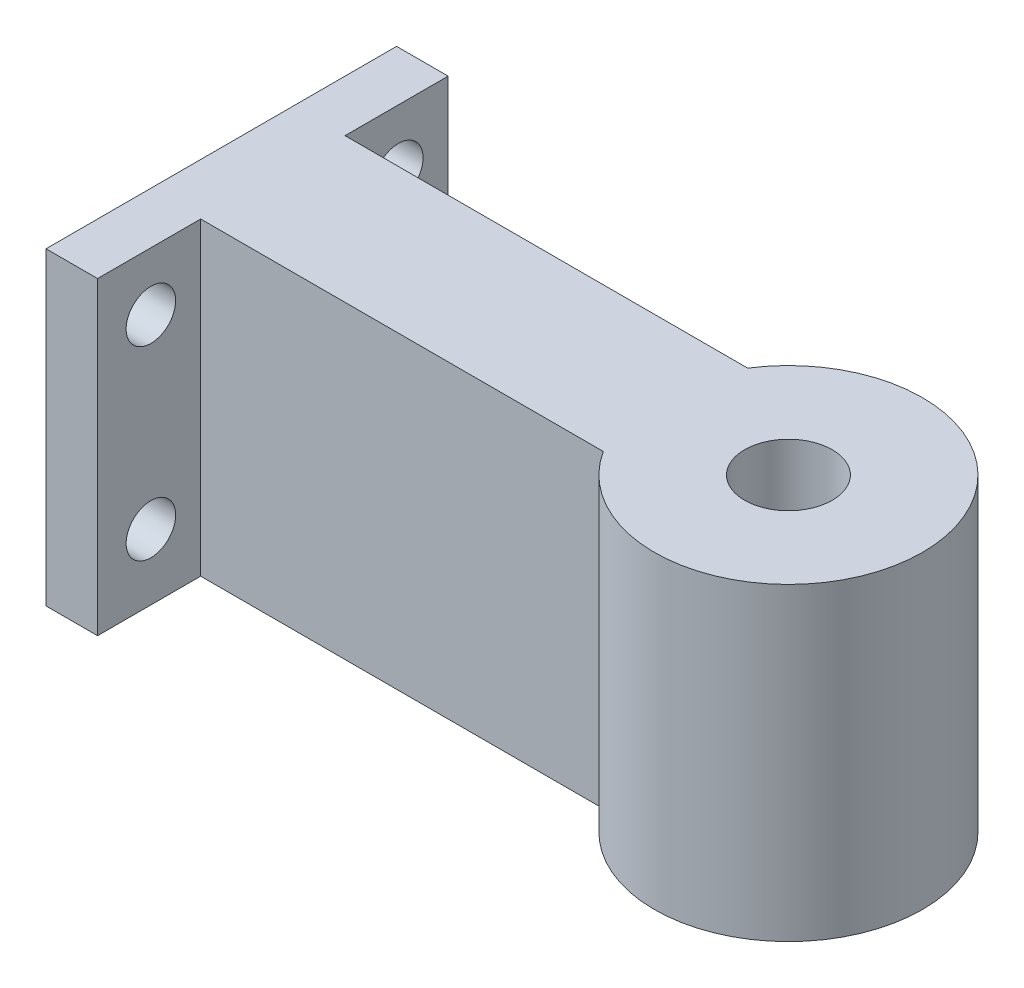
SolidWorks part; units mm, degrees
ref_plane "Front Plane" through (0, 0, 0) normal (0, 0, 1) x (1, 0, 0)
ref_plane "Top Plane" through (0, 0, 0) normal (0, 1, 0) x (1, 0, 0)
ref_plane "Right Plane" through (0, 0, 0) normal (1, 0, 0) x (0, 0, -1)
sketch "Sketch2" plane through (0, 0, 0) normal (0, 1, 0) x (1, 0, 0)
  line L0 (0, 17) -> (0, -17)
  line L1 (0, -17) -> (5, -17)
  line L2 (5, -17) -> (5, -7)
  line L3 (5, -7) -> (44.0455, -7)
  line L4 (44.0455, 7) -> (5, 7)
  line L5 (5, 7) -> (5, 17)
  line L6 (5, 17) -> (0, 17)
  arc A0 (44.0455, 7) -> (44.0455, -7) centre (55, 0) cw
  circle A1 centre (55, 0) radius 4.25
  point P8 (0, 0)
  point P10 (48.2624, 8.3291)
  point P12 (45.6126, 7)
  dimension "D2" = 8.5
  dimension "D6" = 13
  dimension "D1" = 34
  dimension "D3" = 50
  dimension "D4" = 10
  dimension "D5" = 5
extrude "Boss-Extrude1" add sketch "Sketch2" along normal blind 30
sketch "Sketch3" plane through (0, 0, 0) normal (0, -1, 0) x (1, 0, 0)
  circle A0 centre (55, 0) radius 4.25
  circle A1 centre (55, 0) radius 5.25
  circle A2 centre (55, 0) radius 11.25
  circle A3 centre (55, 0) radius 4.25 construction
  circle M12 centre (55, 0) radius 4.25
  dimension "D1" = 10.5
  dimension "D2" = 22.5
extrude "Cut-Extrude1" cut sketch "Sketch3" against normal blind 5 contours A1 M12 | A2 A1 region at (49.8985, 0, 0) region at (44.0682, 0, 0)
extrude "Cut-Extrude2" cut sketch "Sketch3<3>" against normal blind 10.6 from surface contours A1 M12 region at (49.8985, 0, 0) starting at face at (55, 5, -4.25)
sketch "Sketch3<3>" plane through (0, 0, 0) normal (0, -1, 0) x (1, 0, 0) same geometry as "Sketch3"
sketch "Sketch4" plane through (5, 0, 0) normal (1, 0, 0) x (0, 0, -1)
  circle A0 centre (12.1719, 24.3634) radius 2.4
  circle A1 centre (12.1719, 6.3634) radius 2.4
  circle A2 centre (-11.8281, 6.3634) radius 2.4
  circle A3 centre (-11.8281, 24.3634) radius 2.4
  point P8 (0, 0)
  point P9 (0, 0)
  point P10 (0, 0)
  point P11 (0, 0)
  point P12 (0, 0)
  point P13 (-11.8757, 25.6513)
  point P14 (-12.4949, 24.2125)
  point P15 (-12.077, 24.1536)
  point P16 (-12.0178, 24.2673)
  point P17 (-11.8281, 24.3634)
  dimension "D1" = 4.8
  dimension "D2" = 24
  dimension "D3" = 18
extrude "Cut-Extrude3" cut sketch "Sketch4" against normal through all
